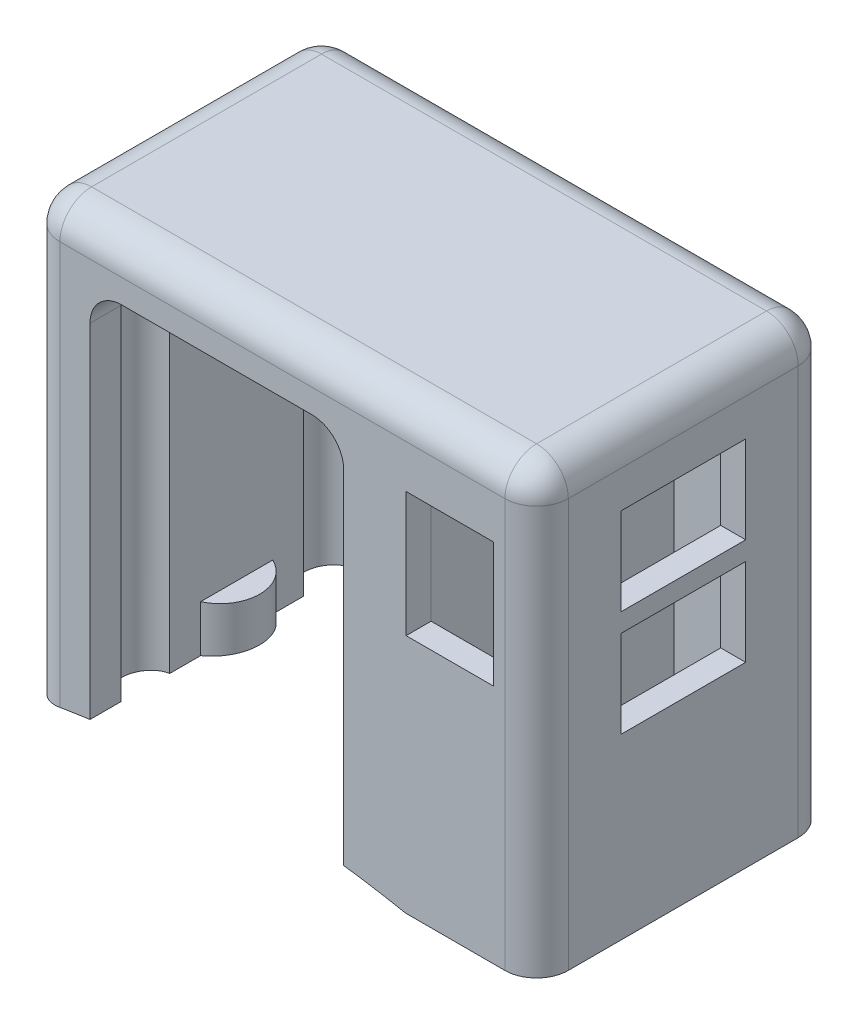
SolidWorks part; units mm, degrees
ref_plane "Front Plane" through (0, 0, 0) normal (0, 0, 1) x (1, 0, 0)
ref_plane "Top Plane" through (0, 0, 0) normal (0, 1, 0) x (1, 0, 0)
ref_plane "Right Plane" through (0, 0, 0) normal (1, 0, 0) x (0, 0, -1)
sketch "Sketch1" plane through (0, 0, 0) normal (0, 0, 1) x (1, 0, 0)
  line L1 (0, 0) -> (60.452, 0)
  line L2 (0, 0) -> (0, -71.12)
  line L3 (0, -71.12) -> (60.452, -71.12)
  line L4 (60.452, 0) -> (60.452, -71.12)
  dimension "D1" = 60.452
  dimension "D2" = 71.12
extrude "Boss-Extrude1" add sketch "Sketch1" along normal blind 46.99
sketch "Sketch2" plane through (0, 0, 46.99) normal (0, 0, 1) x (1, 0, 0)
  line L0 (9.906, -94.2107) -> (9.906, -8.89)
  line L1 (9.906, -94.2107) -> (50.546, -94.2107)
  line L2 (9.906, -8.89) -> (50.546, -8.89)
  line L3 (50.546, -94.2107) -> (50.546, -8.89)
  line L4 (30.226, -8.89) -> (30.226, -94.2107) construction
  line L5 (9.906, -51.5504) -> (50.546, -51.5504) construction
  line L8 (60.452, 0) -> (0, 0) construction
  point P1 (30.226, -51.5504)
  point P8 (30.226, 0)
  dimension "D1" = 8.89
  dimension "D3" = 40.64
extrude "Cut-Extrude1" cut sketch "Sketch2" against normal blind 46.99
sketch "Sketch3" plane through (0, -71.12, 0) normal (0, -1, 0) x (1, 0, 0)
  line L1 (7.2517, 23.495) -> (53.2003, 23.495)
  line L3 (60.452, 46.99) -> (60.452, 0) construction
  line L4 (0, 46.99) -> (0, 0) construction
  line L5 (50.546, 46.99) -> (60.452, 46.99) construction
  circle A0 centre (53.2003, 23.495) radius 2.4448
  circle A1 centre (7.2517, 23.495) radius 2.4448
  dimension "D1" = 45.9486
  dimension "D2" = 4.8895
  dimension "D3" = 7.2517
  dimension "D6" = 4.8895
  dimension "D4" = 7.2517
  dimension "D5" = 23.495
  dimension "D8" = 23.495
extrude "Cut-Extrude2" cut sketch "Sketch3" against normal blind 30.734 contours A1 | A0
sketch "Sketch5" plane through (0, -71.12, 0) normal (0, -1, 0) x (1, 0, 0)
  line L0 (46.8503, 23.495) -> (13.6017, 23.495) construction
  line L1 (53.2003, 23.495) -> (7.2517, 23.495) construction
  circle A0 centre (7.2517, 23.495) radius 6.35
  circle A1 centre (53.2003, 23.495) radius 6.35
  dimension "D1" = 12.7
extrude "Boss-Extrude4" add sketch "Sketch5" against normal blind 9.652
extrude "Cut-Extrude3" cut sketch "Sketch3<5>" against normal blind 38.1 contours A1 | A0 region at (53.2003, -71.12, 25.8706) region at (4.8761, -71.12, 23.495)
sketch "Sketch3<5>" plane through (0, -71.12, 0) normal (0, -1, 0) x (1, 0, 0) same geometry as "Sketch3"
sketch "Sketch8" plane through (0, 0, 46.99) normal (0, 0, 1) x (1, 0, 0)
  circle A0 centre (30.4735, -219.964) radius 152.4
  dimension "D1" = 304.8
fillet "Fillet1" radius 5.08 7 edges at (0, -35.56, 46.99) (0, -35.56, 0) (30.226, 0, 46.99) (30.226, 0, 0) (9.906, -8.89, 23.495) (50.546, -8.89, 23.495) (0, 0, 23.495)
sketch "Sketch9" plane through (0, -8.89, 0) normal (0, -1, 0) x (1, 0, 0)
  line L0 (14.986, 23.495) -> (45.466, 23.495)
  line L1 (14.986, 46.99) -> (14.986, 0) construction
  line L2 (45.466, 0) -> (45.466, 46.99) construction
  line L3 (45.466, 46.99) -> (14.986, 46.99) construction
  circle A0 centre (30.226, 37.0423) radius 5.7371
  circle A1 centre (30.226, 9.9477) radius 5.7371
  dimension "D1" = 9.9477
extrude "Cut-Extrude6" cut sketch "Sketch9" against normal blind 4.572 contours A0 | A1 region at (30.226, -8.89, 37.0423) region at (30.226, -8.89, 9.9477)
sketch "Sketch10" plane through (0, -71.12, 0) normal (0, -1, 0) x (-1, 0, 0)
  line L0 (-9.906, -29.2636) -> (-9.906, -46.99) construction
  line L1 (-50.546, -17.7264) -> (-50.546, 0) construction
  line L3 (-45.466, 0) -> (-14.986, 0) construction
  line L4 (-60.452, -23.495) -> (0, -23.495) construction
  line L5 (-60.452, -46.99) -> (-60.452, 0) construction
  line L6 (0, -41.91) -> (0, -5.08) construction
  line L7 (-50.546, -8.8632) -> (-9.906, -8.8632) construction
  line L8 (-9.906, -8.8632) -> (-9.906, -38.1268) construction
  line L9 (-30.226, -23.495) -> (-30.226, 0) construction
  line L10 (-50.546, -46.99) -> (-50.546, -29.2636) construction
  circle A0 centre (-9.906, -38.1268) radius 3.9006
  circle A1 centre (-9.906, -8.8632) radius 3.9006
  circle A2 centre (-50.546, -38.1268) radius 3.9006
  circle A3 centre (-50.546, -8.8632) radius 3.9006
  dimension "D1" = 7.8013
  dimension "D2" = 29.2636
  dimension "D3" = 40.64
extrude "Cut-Extrude10" cut sketch "Sketch10" against normal up to surface (62.23 mm away) up to face at (30.226, -8.89, 23.495)
extrude "Cut-Extrude11" cut sketch "Sketch8" against normal blind 55.372
sketch "Sketch11" plane through (60.452, 0, 0) normal (1, 0, 0) x (0, 0, -1)
  line L0 (-41.91, 0) -> (-5.08, 0)
  line L1 (-46.99, -70.5416) -> (0, -70.5416)
  line L2 (-46.99, -70.5416) -> (-46.99, -5.08)
  line L3 (-46.99, -5.08) -> (0, -5.08)
  line L4 (0, -70.5416) -> (0, -5.08)
  arc A0 (-41.91, 0) -> (-45.8806, -1.9113) centre (-41.91, -5.08) ccw
  arc A2 (-41.91, 0) -> (-46.99, -5.08) centre (-41.91, -5.08) ccw construction
  arc A3 (0, -5.08) -> (-5.08, 0) centre (-5.08, -5.08) ccw construction
  line M5 (-46.99, -5.08) -> (-46.99, -70.5416)
  line M6 (-46.99, -70.5416) -> (0, -70.5416)
  line M7 (0, -70.5416) -> (0, -5.08)
  arc M8 (0, -5.08) -> (-5.08, 0) centre (-5.08, -5.08) ccw
  line M9 (-5.08, 0) -> (-41.91, 0)
  arc M10 (-41.91, 0) -> (-46.99, -5.08) centre (-41.91, -5.08) ccw
extrude "Boss-Extrude6" add sketch "Sketch11" along normal blind 21 contours L3 M10 M8 M9 | L3 M5 M6 M7 region at (60.452, -2.6084, 23.495) region at (60.452, -37.8108, 23.495)
sketch "Sketch12" plane through (0, -70.5416, 0) normal (0, -1, 0) x (-1, 0, 0)
  line L0 (-60.452, -46.99) -> (-60.452, 0) construction
  line L1 (-60.452, -4) -> (-77.452, -4)
  line L2 (-60.452, -4) -> (-60.452, -42.99)
  line L3 (-60.452, -42.99) -> (-77.452, -42.99)
  line L4 (-77.452, -4) -> (-77.452, -42.99)
  line L5 (-81.452, -46.99) -> (-81.452, 0) construction
  dimension "D1" = 4
  dimension "D2" = 4
  dimension "D3" = 4
extrude "Cut-Extrude12" cut sketch "Sketch12" against normal blind 63
sketch "Sketch22" plane through (50.546, 0, 0) normal (-1, 0, 0) x (0, 0, 1)
  circle A0 centre (8.8632, -57.6558) radius 3.9006
sketch "Sketch24" plane through (0, 0, 0) normal (-1, 0, 0) x (0, 0, 1)
  line L0 (8.8632, -71.12) -> (8.8632, -65.6637)
  line L1 (4.9625, -71.12) -> (12.7638, -71.12) construction
  line L2 (12.6464, -65.6637) -> (12.6464, -70.6418)
  line L3 (5.08, -70.6418) -> (41.91, -70.6418) construction
  line L4 (12.6464, -70.6418) -> (5.08, -70.6418)
  line L5 (5.08, -70.6418) -> (5.0979, -65.2957)
  circle A0 centre (8.8632, -65.6637) radius 3.7832
fillet "Fillet2" radius 5.08 5 edges at (81.452, -1.4879, 1.4879) (81.452, -1.4879, 45.5021) (81.452, -37.8108, 46.99) (81.452, 0, 23.495) (81.452, -37.8108, 0)
sketch "Sketch25" plane through (81.452, 0, 0) normal (1, 0, 0) x (0, 0, -1)
  line L0 (-46.99, -70.5416) -> (-46.99, -5.08) construction
  line L1 (-33.49, -11) -> (-13.49, -11)
  line L2 (-33.49, -11) -> (-33.49, -25)
  line L3 (-33.49, -25) -> (-13.49, -25)
  line L4 (-13.49, -11) -> (-13.49, -25)
  line L5 (-33.49, -28) -> (-13.49, -28)
  line L6 (-33.49, -28) -> (-33.49, -42)
  line L7 (-33.49, -42) -> (-13.49, -42)
  line L8 (-13.49, -28) -> (-13.49, -42)
  line L10 (-41.91, 0) -> (-5.08, 0) construction
  dimension "D1" = 20
  dimension "D2" = 14
  dimension "D3" = 20
  dimension "D4" = 14
  dimension "D5" = 13.5
  dimension "D6" = 13.5
  dimension "D7" = 11
  dimension "D8" = 28
extrude "Cut-Extrude13" cut sketch "Sketch25" against normal blind 10
sketch "Sketch26" plane through (0, 0, 46.99) normal (0, 0, 1) x (1, 0, 0)
  line L0 (5.08, 0) -> (76.372, 0) construction
  line L1 (60.546, -12) -> (74.546, -12)
  line L2 (60.546, -12) -> (60.546, -32)
  line L3 (60.546, -32) -> (74.546, -32)
  line L4 (74.546, -12) -> (74.546, -32)
  line L5 (50.546, -68.8916) -> (50.546, -13.97) construction
  dimension "D1" = 14
  dimension "D2" = 20
  dimension "D3" = 12
  dimension "D4" = 10
extrude "Cut-Extrude14" cut sketch "Sketch26" against normal blind 10
